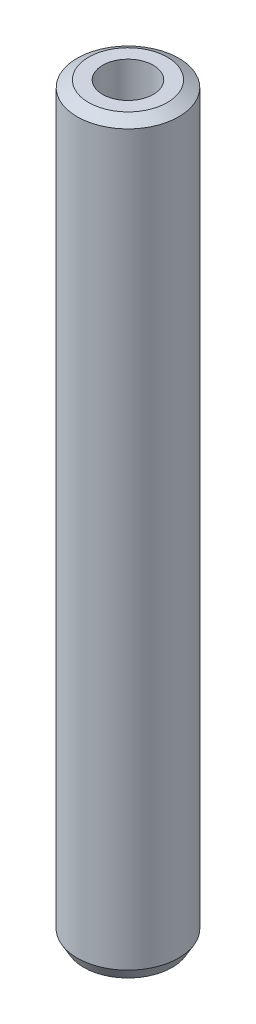
SolidWorks part; units mm, degrees
ref_plane "Front Plane" through (0, 0, 0) normal (0, 0, 1) x (1, 0, 0)
ref_plane "Top Plane" through (0, 0, 0) normal (0, 1, 0) x (1, 0, 0)
ref_plane "Right Plane" through (0, 0, 0) normal (1, 0, 0) x (0, 0, -1)
sketch "Sketch1" plane through (0, 0, 0) normal (0, 1, 0) x (1, 0, 0)
  circle A0 centre (0, 0) radius 12.5
  dimension "SHAFT_OD" = 25
extrude "Boss-Extrude1" add sketch "Sketch1" along normal blind 183.7584
sketch "Sketch2" plane through (0, 0, 0) normal (0, 1, 0) x (1, 0, 0)
  circle A0 centre (0, 0) radius 6.2321
  dimension "BORE_D" = 12.4642
extrude "Cut-Extrude1" cut sketch "Sketch2" along normal through all
chamfer "Chamfer1" distance 1.6273 angle 60 2 edges at (0, 183.7584, 12.5) (0, 0, 12.5) first distance on face at (0, 183.7584, 12.5) first distance on face at (0, 0, 6.2321)
